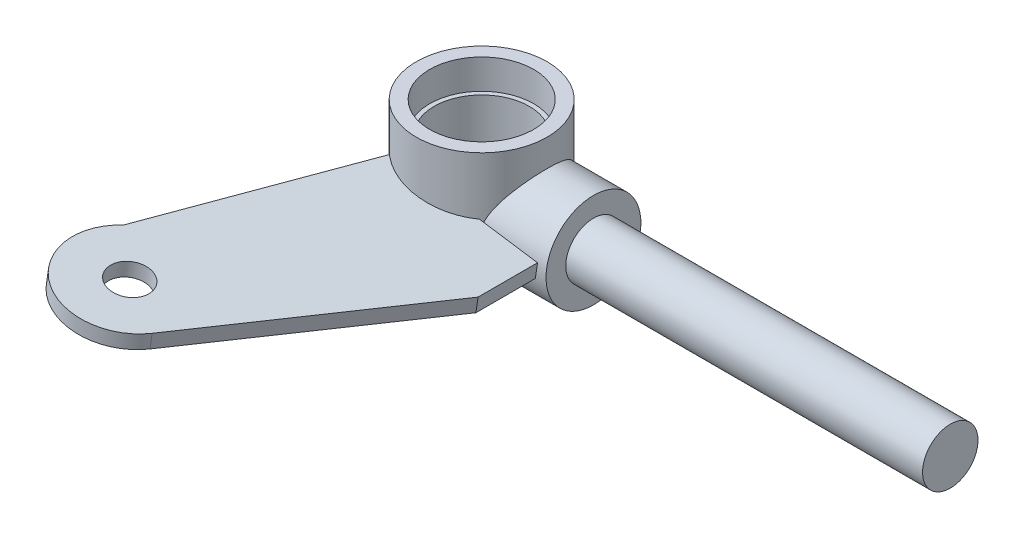
SolidWorks part; units mm, degrees
ref_plane "Front Plane" through (0, 0, 0) normal (0, 0, 1) x (1, 0, 0)
ref_plane "Top Plane" through (0, 0, 0) normal (0, 1, 0) x (1, 0, 0)
ref_plane "Right Plane" through (0, 0, 0) normal (1, 0, 0) x (0, 0, -1)
sketch "Sketch2" plane through (0, 0, 0) normal (0, 0, 1) x (1, 0, 0)
  line L0 (0, -12.3825) -> (0, 12.3825) construction
  line L1 (0, 12.3825) -> (13.97, 12.3825) construction
  line L2 (13.97, 12.3825) -> (13.97, -12.3825)
  line L3 (13.97, -12.3825) -> (0, -12.3825) construction
  line L4 (13.97, 12.3825) -> (11.1125, 12.3825)
  line L5 (11.1125, 12.3825) -> (11.1125, 6.0325)
  line L6 (11.1125, 6.0325) -> (10.16, 6.0325)
  line L7 (10.16, 6.0325) -> (10.16, -6.0325)
  line L8 (10.16, 0) -> (13.97, 0) construction
  line L9 (13.97, -12.3825) -> (11.1125, -12.3825)
  line L10 (11.1125, -12.3825) -> (11.1125, -6.0325)
  line L11 (11.1125, -6.0325) -> (10.16, -6.0325)
  point P4 (0, 0)
  dimension "D1" = 24.765
  dimension "D2" = 13.97
  dimension "D3" = 11.1125
  dimension "D4" = 10.16
  dimension "D5" = 6.35
revolve "Revolve1" add sketch "Sketch2" angle 360 about L0
sketch "Sketch3" plane through (0, 0, 0) normal (0, 1, 0) x (1, 0, 0)
  line L0 (0, 0) -> (0, 5.4477) construction
  circle A0 centre (0, 0) radius 5.4477
ref_plane "Plane1" through (0, 0, 0) normal (-0.1478, 0.989, 0) x (0, 0, -1)
sketch "Sketch4" plane through (0, 0, 0) normal (-0.1478, 0.989, 0) x (0, 0, -1)
  line L0 (-10.3829, -9.3464) -> (-54.0399, -22.9253)
  line L1 (-10.16, 22.098) -> (-22.86, 22.098)
  line L2 (-22.86, 22.098) -> (-67.9997, -2.6237)
  line L3 (-64.9708, -16.4023) -> (-70.8087, -22.2387) construction
  line L4 (-70.8087, -22.2387) -> (-81.8236, -11.2209) construction
  line L5 (-81.8236, -11.2209) -> (-75.9789, -17.0671) construction
  line L6 (-64.9708, -16.4023) -> (-69.1683, -12.2037) construction
  line L7 (0, 0) -> (0, 24.13) construction
  line L8 (-10.16, 24.13) -> (10.16, 24.13) construction
  line L9 (10.16, 24.13) -> (10.16, 9.5883) construction
  line L10 (-10.16, 24.13) -> (-10.16, 9.5883) construction
  line L11 (0, 13.97) -> (0, 24.13) construction
  line L12 (0, 0) -> (5.4477, 0) construction
  line L13 (-10.16, 22.098) -> (-10.16, 9.5883)
  arc A0 (-67.9997, -2.6237) -> (-54.0399, -22.9253) centre (-62.0518, -13.4841) ccw
  circle A1 centre (-62.0518, -13.4841) radius 4.1275
  circle A2 centre (0, 0) radius 13.97 construction
  arc A3 (-10.16, 9.5883) -> (-10.3829, -9.3464) centre (0, 0) ccw
  point P15 (0, 24.13)
  point P22 (10.16, 24.13)
  dimension "D1" = 8.255
  dimension "D2" = 27.94
  dimension "D3" = 63.5
  dimension "D4" = 8.255
  dimension "D5" = 20.32
  dimension "D6" = 2.032
  dimension "D7" = 10.16
  dimension "D8" = 12.7
  dimension "D9" = 45.72
  dimension "D10" = 31.4452
  dimension "D11" = 24.638
extrude "Boss-Extrude2" add sketch "Sketch4" along normal blind 1.5875 and the other way blind 1.5875 separate body contours A3 L13 L1 L2 A0 L0 A1 region at (2.6031, 0.389, 39.3707)
ref_plane "Plane2" through (-13.97, 0, 0) normal (-1, 0, 0) x (0, 0, 1)
sketch "Sketch5" plane through (-13.97, 0, 0) normal (-1, 0, 0) x (0, 0, 1)
  circle A0 centre (0, -3.5666) radius 10.1309
extrude "Boss-Extrude3" add sketch "Sketch5" along normal up to vertex and the other way up to surface separate body up to point (-23.865, -3.5666, 10.16) other way up to face at (0, 12.3825, -13.97)
sketch "Sketch6" plane through (-23.865, 0, 0) normal (-1, 0, 0) x (0, 0, 1)
  line L0 (10.16, -3.5666) -> (-10.16, -3.5666) construction
  circle A0 centre (0, -3.5666) radius 5.9211
extrude "Boss-Extrude4" add sketch "Sketch6" along normal blind 76.2
ref_plane "Spindle Midplane" through (0, -3.5666, 0) normal (0, 1, 0) x (1, 0, 0)
mirror "Mirror1" about plane through (-100.065, -3.5666, 0) normal (-1, 0, 0) of bodies 102 104 101
sketch "Sketch7" plane through (0, 0, 0) normal (0, 1, 0) x (1, 0, 0)
  line L0 (-100.065, 5.9211) -> (-100.065, 59.5798) construction
  line L2 (-100.065, 59.5798) -> (49.5782, 59.5798)
  line L3 (-100.065, 59.5798) -> (-100.065, -110.6588)
  line L4 (-100.065, -110.6588) -> (49.5782, -110.6588)
  line L5 (49.5782, 59.5798) -> (49.5782, -110.6588)
  line L6 (-100.065, 59.5798) -> (49.5782, -110.6588) construction
  line L7 (-100.065, -110.6588) -> (49.5782, 59.5798) construction
  point P6 (-25.2434, -25.5395)
extrude "Cut-Extrude1" cut sketch "Sketch7" against normal through all both and the other way through all
